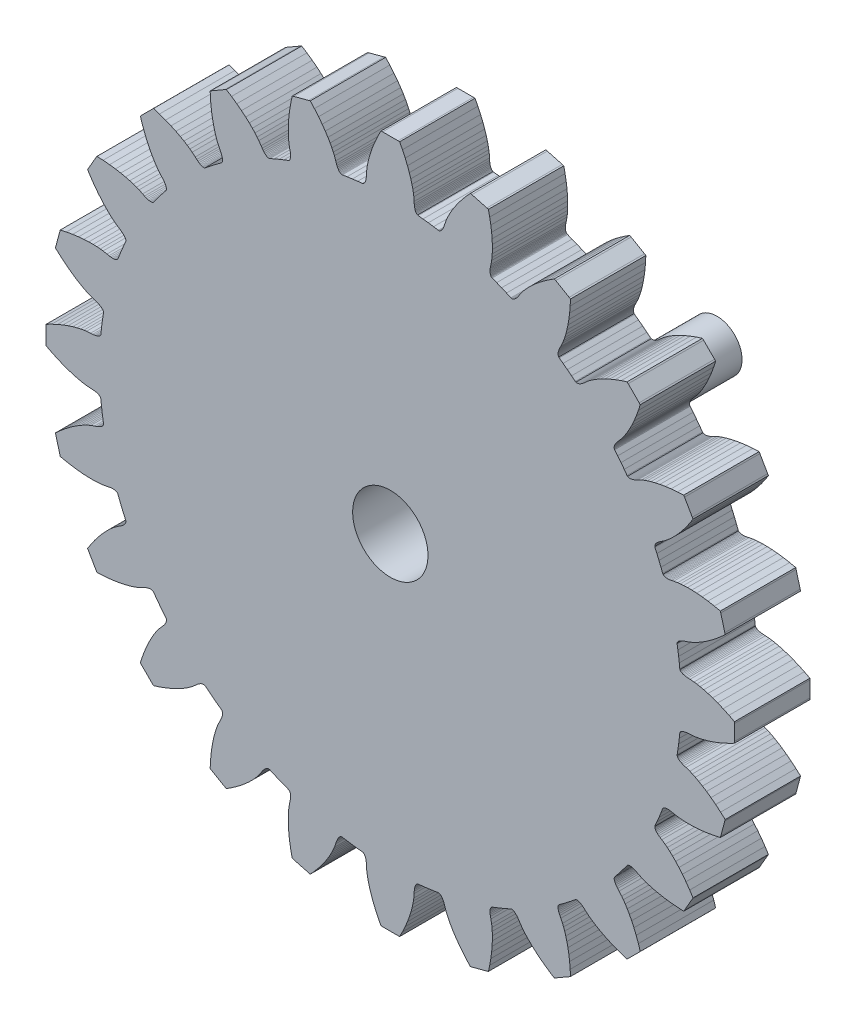
SolidWorks part; units mm, degrees
ref_plane "Front Plane" through (0, 0, 0) normal (0, 0, 1) x (1, 0, 0)
ref_plane "Top Plane" through (0, 0, 0) normal (0, 1, 0) x (1, 0, 0)
ref_plane "Right Plane" through (0, 0, 0) normal (1, 0, 0) x (0, 0, -1)
sketch "Sketch2" plane through (0, 0, 0) normal (0, 0, 1) x (1, 0, 0)
  line L1176 (3.2896, 23.0036) -> (3.0389, 22.7942)
  line L1177 (3.0389, 22.7942) -> (2.8021, 22.6117)
  line L1178 (2.8021, 22.6117) -> (2.5789, 22.4544)
  line L1179 (2.5789, 22.4544) -> (2.3725, 22.3218)
  line L1180 (2.3725, 22.3218) -> (2.182, 22.2103)
  line L1181 (2.182, 22.2103) -> (2.0109, 22.1191)
  line L1182 (2.0109, 22.1191) -> (1.8618, 22.048)
  line L1183 (1.8618, 22.048) -> (1.7314, 21.9922)
  line L1184 (1.7314, 21.9922) -> (1.5416, 21.9241)
  line L1185 (1.5416, 21.9241) -> (1.4393, 21.8922)
  line L1186 (1.4393, 21.8922) -> (1.3698, 21.8662)
  line L1187 (1.3698, 21.8662) -> (1.3083, 21.8387)
  line L1188 (1.3083, 21.8387) -> (1.2546, 21.8097)
  line L1189 (1.2546, 21.8097) -> (1.2083, 21.7799)
  line L1190 (1.2083, 21.7799) -> (1.1698, 21.7495)
  line L1191 (1.1698, 21.7495) -> (1.1387, 21.7184)
  line L1192 (1.1387, 21.7184) -> (1.1155, 21.6879)
  line L1193 (1.1155, 21.6879) -> (1.1004, 21.6575)
  line L1194 (1.1004, 21.6575) -> (1.0924, 21.627)
  line L1195 (1.0924, 21.627) -> (1.093, 21.5916)
  line L1196 (1.093, 21.5916) -> (1.1307, 21.3526)
  line L1197 (1.1307, 21.3526) -> (1.1683, 21.0852)
  line L1198 (1.1683, 21.0852) -> (1.2011, 20.818)
  line L1199 (1.2011, 20.818) -> (1.2264, 20.5774)
  line L1200 (1.2264, 20.5774) -> (1.2351, 20.542)
  line L1201 (1.2351, 20.542) -> (1.2503, 20.5151)
  line L1202 (1.2503, 20.5151) -> (1.2736, 20.4896)
  line L1203 (1.2736, 20.4896) -> (1.304, 20.4665)
  line L1204 (1.304, 20.4665) -> (1.3417, 20.4448)
  line L1205 (1.3417, 20.4448) -> (1.3865, 20.4253)
  line L1206 (1.3865, 20.4253) -> (1.4393, 20.4086)
  line L1207 (1.4393, 20.4086) -> (1.4988, 20.3942)
  line L1208 (1.4988, 20.3942) -> (1.5655, 20.384)
  line L1209 (1.5655, 20.384) -> (1.6388, 20.3767)
  line L1210 (1.6388, 20.3767) -> (1.7459, 20.3724)
  line L1211 (1.7459, 20.3724) -> (1.9474, 20.3558)
  line L1212 (1.9474, 20.3558) -> (2.0872, 20.3354)
  line L1213 (2.0872, 20.3354) -> (2.2499, 20.305)
  line L1214 (2.2499, 20.305) -> (2.4391, 20.2616)
  line L1215 (2.4391, 20.2616) -> (2.6514, 20.203)
  line L1216 (2.6514, 20.203) -> (2.8854, 20.1275)
  line L1217 (2.8854, 20.1275) -> (3.1418, 20.034)
  line L1218 (3.1418, 20.034) -> (3.4178, 19.9188)
  line L1219 (3.4178, 19.9188) -> (3.7134, 19.7813)
  line L1220 (3.7134, 19.7813) -> (3.9915, 19.6379)
  line L1221 (3.9915, 19.6379) -> (3.9938, 19.5596)
  line L1222 (3.9938, 19.5596) -> (3.9938, 18.7742)
  line L1223 (3.9938, 18.7742) -> (3.9915, 18.6954)
  line L1224 (3.9915, 18.6954) -> (3.7134, 18.5525)
  line L1225 (3.7134, 18.5525) -> (3.4178, 18.415)
  line L1226 (3.4178, 18.415) -> (3.1418, 18.2998)
  line L1227 (3.1418, 18.2998) -> (2.8854, 18.2056)
  line L1228 (2.8854, 18.2056) -> (2.6514, 18.131)
  line L1229 (2.6514, 18.131) -> (2.4391, 18.0722)
  line L1230 (2.4391, 18.0722) -> (2.2499, 18.0288)
  line L1231 (2.2499, 18.0288) -> (2.0872, 17.9984)
  line L1232 (2.0872, 17.9984) -> (1.9474, 17.9781)
  line L1233 (1.9474, 17.9781) -> (1.7459, 17.9616)
  line L1234 (1.7459, 17.9616) -> (1.6388, 17.9571)
  line L1235 (1.6388, 17.9571) -> (1.5655, 17.9498)
  line L1236 (1.5655, 17.9498) -> (1.4988, 17.9391)
  line L1237 (1.4988, 17.9391) -> (1.4393, 17.9252)
  line L1238 (1.4393, 17.9252) -> (1.3865, 17.9085)
  line L1239 (1.3865, 17.9085) -> (1.3417, 17.889)
  line L1240 (1.3417, 17.889) -> (1.304, 17.8673)
  line L1241 (1.304, 17.8673) -> (1.2736, 17.8434)
  line L1242 (1.2736, 17.8434) -> (1.2503, 17.818)
  line L1243 (1.2503, 17.818) -> (1.2351, 17.7913)
  line L1244 (1.2351, 17.7913) -> (1.2264, 17.7565)
  line L1245 (1.2264, 17.7565) -> (1.2011, 17.516)
  line L1246 (1.2011, 17.516) -> (1.1683, 17.2478)
  line L1247 (1.1683, 17.2478) -> (1.1307, 16.9813)
  line L1248 (1.1307, 16.9813) -> (1.093, 16.7423)
  line L1249 (1.093, 16.7423) -> (1.0924, 16.706)
  line L1250 (1.0924, 16.706) -> (1.1004, 16.6763)
  line L1251 (1.1004, 16.6763) -> (1.1155, 16.6459)
  line L1252 (1.1155, 16.6459) -> (1.1387, 16.6155)
  line L1253 (1.1387, 16.6155) -> (1.1698, 16.5843)
  line L1254 (1.1698, 16.5843) -> (1.2083, 16.5539)
  line L1255 (1.2083, 16.5539) -> (1.2546, 16.5243)
  line L1256 (1.2546, 16.5243) -> (1.3083, 16.4953)
  line L1257 (1.3083, 16.4953) -> (1.3698, 16.4676)
  line L2458 (1.3698, 16.4676) -> (1.4393, 16.4416)
  line L2459 (1.4393, 16.4416) -> (1.5416, 16.4097)
  line L2460 (1.5416, 16.4097) -> (1.7314, 16.3416)
  line L2461 (1.7314, 16.3416) -> (1.8618, 16.2859)
  line L2462 (1.8618, 16.2859) -> (2.0109, 16.2142)
  line L2463 (2.0109, 16.2142) -> (2.182, 16.1235)
  line L2464 (2.182, 16.1235) -> (2.3725, 16.012)
  line L2465 (2.3725, 16.012) -> (2.5789, 15.8788)
  line L2466 (2.5789, 15.8788) -> (2.8021, 15.7215)
  line L2467 (2.8021, 15.7215) -> (3.0389, 15.5396)
  line L2468 (3.0389, 15.5396) -> (3.2896, 15.3296)
  line L2469 (3.2896, 15.3296) -> (3.5207, 15.1195)
  line L2470 (3.5207, 15.1195) -> (3.5018, 15.0434)
  line L2471 (3.5018, 15.0434) -> (3.2991, 14.2842)
  line L2472 (3.2991, 14.2842) -> (3.2766, 14.2089)
  line L2473 (3.2766, 14.2089) -> (2.9715, 14.1429)
  line L2474 (2.9715, 14.1429) -> (2.65, 14.0864)
  line L2475 (2.65, 14.0864) -> (2.3537, 14.0466)
  line L2476 (2.3537, 14.0466) -> (2.0811, 14.0219)
  line L2477 (2.0811, 14.0219) -> (1.8364, 14.0105)
  line L2478 (1.8364, 14.0105) -> (1.6155, 14.009)
  line L2479 (1.6155, 14.009) -> (1.4221, 14.0155)
  line L2480 (1.4221, 14.0155) -> (1.2569, 14.0285)
  line L2481 (1.2569, 14.0285) -> (1.1163, 14.0452)
  line L2482 (1.1163, 14.0452) -> (0.9179, 14.0814)
  line L2483 (0.9179, 14.0814) -> (0.8126, 14.1046)
  line L2484 (0.8126, 14.1046) -> (0.7404, 14.1169)
  line L2485 (0.7404, 14.1169) -> (0.6731, 14.1234)
  line L2486 (0.6731, 14.1234) -> (0.6121, 14.1256)
  line L2487 (0.6121, 14.1256) -> (0.5572, 14.1226)
  line L2488 (0.5572, 14.1226) -> (0.5086, 14.1162)
  line L2489 (0.5086, 14.1162) -> (0.4664, 14.1046)
  line L2490 (0.4664, 14.1046) -> (0.431, 14.0894)
  line L2491 (0.431, 14.0894) -> (0.402, 14.0712)
  line L2492 (0.402, 14.0712) -> (0.3801, 14.0488)
  line L2493 (0.3801, 14.0488) -> (0.3629, 14.0177)
  line L2494 (0.3629, 14.0177) -> (0.276, 13.7916)
  line L2495 (0.276, 13.7916) -> (0.1753, 13.5416)
  line L2496 (0.1753, 13.5416) -> (0.0703, 13.2939)
  line L2497 (0.0703, 13.2939) -> (-0.0283, 13.0723)
  line L2498 (-0.0283, 13.0723) -> (-0.0383, 13.0382)
  line L2499 (-0.0383, 13.0382) -> (-0.0383, 13.007)
  line L2500 (-0.0383, 13.007) -> (-0.0311, 12.9737)
  line L2501 (-0.0311, 12.9737) -> (-0.0167, 12.9376)
  line L2502 (-0.0167, 12.9376) -> (0.0051, 12.8999)
  line L2503 (0.0051, 12.8999) -> (0.0339, 12.8608)
  line L2504 (0.0339, 12.8608) -> (0.0709, 12.8202)
  line L2505 (0.0709, 12.8202) -> (0.1159, 12.7781)
  line L2506 (0.1159, 12.7781) -> (0.1681, 12.7354)
  line L2507 (0.1681, 12.7354) -> (0.2282, 12.6927)
  line L2508 (0.2282, 12.6927) -> (0.3186, 12.6354)
  line L2509 (0.3186, 12.6354) -> (0.4846, 12.5202)
  line L2510 (0.4846, 12.5202) -> (0.5955, 12.4326)
  line L2511 (0.5955, 12.4326) -> (0.7214, 12.3254)
  line L2512 (0.7214, 12.3254) -> (0.8635, 12.1928)
  line L2513 (0.8635, 12.1928) -> (1.0185, 12.0356)
  line L2514 (1.0185, 12.0356) -> (1.1836, 11.8538)
  line L2515 (1.1836, 11.8538) -> (1.3582, 11.6444)
  line L2516 (1.3582, 11.6444) -> (1.5401, 11.4068)
  line L2517 (1.5401, 11.4068) -> (1.727, 11.1395)
  line L2518 (1.727, 11.1395) -> (1.8965, 10.8765)
  line L2519 (1.8965, 10.8765) -> (1.8588, 10.8077)
  line L2520 (1.8588, 10.8077) -> (1.4663, 10.1281)
  line L2521 (1.4663, 10.1281) -> (1.4257, 10.0608)
  line L2522 (1.4257, 10.0608) -> (1.1128, 10.0753)
  line L2523 (1.1128, 10.0753) -> (0.7882, 10.1042)
  line L2524 (0.7882, 10.1042) -> (0.4911, 10.1426)
  line L2525 (0.4911, 10.1426) -> (0.2224, 10.1897)
  line L2526 (0.2224, 10.1897) -> (-0.0174, 10.2412)
  line L2527 (-0.0174, 10.2412) -> (-0.231, 10.2969)
  line L2528 (-0.231, 10.2969) -> (-0.4165, 10.3542)
  line L2529 (-0.4165, 10.3542) -> (-0.573, 10.4092)
  line L2530 (-0.573, 10.4092) -> (-0.7041, 10.4614)
  line L2531 (-0.7041, 10.4614) -> (-0.8868, 10.5476)
  line L2532 (-0.8868, 10.5476) -> (-0.9816, 10.5976)
  line L2533 (-0.9816, 10.5976) -> (-1.0492, 10.628)
  line L2534 (-1.0492, 10.628) -> (-1.1119, 10.6519)
  line L2535 (-1.1119, 10.6519) -> (-1.1708, 10.6693)
  line L2536 (-1.1708, 10.6693) -> (-1.2243, 10.6809)
  line L2537 (-1.2243, 10.6809) -> (-1.2729, 10.6867)
  line L2538 (-1.2729, 10.6867) -> (-1.3163, 10.6867)
  line L2539 (-1.3163, 10.6867) -> (-1.3548, 10.6816)
  line L2540 (-1.3548, 10.6816) -> (-1.3874, 10.6715)
  line L2541 (-1.3874, 10.6715) -> (-1.4141, 10.6555)
  line L2542 (-1.4141, 10.6555) -> (-1.4388, 10.6295)
  line L2543 (-1.4388, 10.6295) -> (-1.5809, 10.4339)
  line L2544 (-1.5809, 10.4339) -> (-1.7431, 10.2187)
  line L2545 (-1.7431, 10.2187) -> (-1.9089, 10.0064)
  line L2546 (-1.9089, 10.0064) -> (-2.0618, 9.8181)
  line L2547 (-2.0618, 9.8181) -> (-2.0799, 9.7877)
  line L2548 (-2.0799, 9.7877) -> (-2.0885, 9.7572)
  line L2549 (-2.0885, 9.7572) -> (-2.09, 9.7232)
  line L2550 (-2.09, 9.7232) -> (-2.0856, 9.6848)
  line L2551 (-2.0856, 9.6848) -> (-2.0741, 9.6428)
  line L2552 (-2.0741, 9.6428) -> (-2.056, 9.5971)
  line L2553 (-2.056, 9.5971) -> (-2.0307, 9.5486)
  line L2554 (-2.0307, 9.5486) -> (-1.9988, 9.4964)
  line L2555 (-1.9988, 9.4964) -> (-1.959, 9.4421)
  line L2556 (-1.959, 9.4421) -> (-1.9119, 9.3849)
  line L2557 (-1.9119, 9.3849) -> (-1.8394, 9.3059)
  line L2558 (-1.8394, 9.3059) -> (-1.7089, 9.1516)
  line L2559 (-1.7089, 9.1516) -> (-1.6243, 9.0386)
  line L2560 (-1.6243, 9.0386) -> (-1.5308, 8.9017)
  line L2561 (-1.5308, 8.9017) -> (-1.428, 8.7372)
  line L2562 (-1.428, 8.7372) -> (-1.3186, 8.546)
  line L2563 (-1.3186, 8.546) -> (-1.2062, 8.3272)
  line L2564 (-1.2062, 8.3272) -> (-1.0917, 8.0794)
  line L2565 (-1.0917, 8.0794) -> (-0.9773, 7.8034)
  line L2566 (-0.9773, 7.8034) -> (-0.8657, 7.497)
  line L2567 (-0.8657, 7.497) -> (-0.7709, 7.1985)
  line L2568 (-0.7709, 7.1985) -> (-0.8252, 7.142)
  line L2569 (-0.8252, 7.142) -> (-1.3802, 6.5871)
  line L2570 (-1.3802, 6.5871) -> (-1.4365, 6.5328)
  line L2571 (-1.4365, 6.5328) -> (-1.7351, 6.6277)
  line L2572 (-1.7351, 6.6277) -> (-2.0415, 6.7392)
  line L2573 (-2.0415, 6.7392) -> (-2.3174, 6.8537)
  line L2574 (-2.3174, 6.8537) -> (-2.5652, 6.9682)
  line L2575 (-2.5652, 6.9682) -> (-2.7841, 7.0805)
  line L2576 (-2.7841, 7.0805) -> (-2.9753, 7.1898)
  line L2577 (-2.9753, 7.1898) -> (-3.1398, 7.2927)
  line L2578 (-3.1398, 7.2927) -> (-3.2767, 7.3862)
  line L2579 (-3.2767, 7.3862) -> (-3.3898, 7.4709)
  line L2580 (-3.3898, 7.4709) -> (-3.544, 7.6013)
  line L2581 (-3.544, 7.6013) -> (-3.623, 7.6738)
  line L2582 (-3.623, 7.6738) -> (-3.6802, 7.7209)
  line L2583 (-3.6802, 7.7209) -> (-3.7345, 7.7607)
  line L2584 (-3.7345, 7.7607) -> (-3.7866, 7.7926)
  line L2585 (-3.7866, 7.7926) -> (-3.8352, 7.8179)
  line L2586 (-3.8352, 7.8179) -> (-3.8809, 7.836)
  line L2587 (-3.8809, 7.836) -> (-3.9229, 7.8476)
  line L2588 (-3.9229, 7.8476) -> (-3.9613, 7.852)
  line L2589 (-3.9613, 7.852) -> (-3.9953, 7.8505)
  line L2590 (-3.9953, 7.8505) -> (-4.0256, 7.8418)
  line L2591 (-4.0256, 7.8418) -> (-4.0561, 7.8237)
  line L2592 (-4.0561, 7.8237) -> (-4.2445, 7.6709)
  line L2593 (-4.2445, 7.6709) -> (-4.4569, 7.505)
  line L2594 (-4.4569, 7.505) -> (-4.672, 7.3427)
  line L2595 (-4.672, 7.3427) -> (-4.8674, 7.2007)
  line L2596 (-4.8674, 7.2007) -> (-4.8936, 7.1761)
  line L2597 (-4.8936, 7.1761) -> (-4.9096, 7.1493)
  line L2598 (-4.9096, 7.1493) -> (-4.9197, 7.1167)
  line L2599 (-4.9197, 7.1167) -> (-4.9248, 7.0783)
  line L2600 (-4.9248, 7.0783) -> (-4.9248, 7.0348)
  line L2601 (-4.9248, 7.0348) -> (-4.9191, 6.9863)
  line L2602 (-4.9191, 6.9863) -> (-4.9073, 6.9327)
  line L2603 (-4.9073, 6.9327) -> (-4.8901, 6.874)
  line L2604 (-4.8901, 6.874) -> (-4.8662, 6.8109)
  line L2605 (-4.8662, 6.8109) -> (-4.8357, 6.7436)
  line L2606 (-4.8357, 6.7436) -> (-4.7857, 6.6487)
  line L2607 (-4.7857, 6.6487) -> (-4.6994, 6.4661)
  line L2608 (-4.6994, 6.4661) -> (-4.6473, 6.335)
  line L2609 (-4.6473, 6.335) -> (-4.5922, 6.1785)
  line L2610 (-4.5922, 6.1785) -> (-4.5349, 5.9931)
  line L2611 (-4.5349, 5.9931) -> (-4.4794, 5.7793)
  line L2612 (-4.4794, 5.7793) -> (-4.4277, 5.5396)
  line L2613 (-4.4277, 5.5396) -> (-4.3807, 5.2708)
  line L2614 (-4.3807, 5.2708) -> (-4.3422, 4.9738)
  line L2615 (-4.3422, 4.9738) -> (-4.3134, 4.6492)
  line L2616 (-4.3134, 4.6492) -> (-4.2988, 4.3363)
  line L2617 (-4.2988, 4.3363) -> (-4.3661, 4.2957)
  line L2618 (-4.3661, 4.2957) -> (-5.0456, 3.9031)
  line L2619 (-5.0456, 3.9031) -> (-5.1144, 3.8654)
  line L2620 (-5.1144, 3.8654) -> (-5.3775, 4.0349)
  line L2621 (-5.3775, 4.0349) -> (-5.6449, 4.2218)
  line L2622 (-5.6449, 4.2218) -> (-5.8825, 4.4037)
  line L2623 (-5.8825, 4.4037) -> (-6.0918, 4.5782)
  line L2624 (-6.0918, 4.5782) -> (-6.2736, 4.7434)
  line L2625 (-6.2736, 4.7434) -> (-6.4309, 4.8984)
  line L2626 (-6.4309, 4.8984) -> (-6.5635, 5.0404)
  line L2627 (-6.5635, 5.0404) -> (-6.6707, 5.1665)
  line L2628 (-6.6707, 5.1665) -> (-6.7584, 5.2773)
  line L2629 (-6.7584, 5.2773) -> (-6.8735, 5.4432)
  line L2630 (-6.8735, 5.4432) -> (-6.9307, 5.5338)
  line L2631 (-6.9307, 5.5338) -> (-6.9735, 5.5939)
  line L2632 (-6.9735, 5.5939) -> (-7.0161, 5.6461)
  line L2633 (-7.0161, 5.6461) -> (-7.0582, 5.691)
  line L2634 (-7.0582, 5.691) -> (-7.0989, 5.7279)
  line L2635 (-7.0989, 5.7279) -> (-7.138, 5.7569)
  line L2636 (-7.138, 5.7569) -> (-7.1757, 5.7786)
  line L2637 (-7.1757, 5.7786) -> (-7.2117, 5.7931)
  line L2638 (-7.2117, 5.7931) -> (-7.2451, 5.8004)
  line L2639 (-7.2451, 5.8004) -> (-7.2764, 5.8004)
  line L2640 (-7.2764, 5.8004) -> (-7.3103, 5.7902)
  line L2641 (-7.3103, 5.7902) -> (-7.5321, 5.6917)
  line L2642 (-7.5321, 5.6917) -> (-7.7799, 5.5867)
  line L2643 (-7.7799, 5.5867) -> (-8.0296, 5.486)
  line L2644 (-8.0296, 5.486) -> (-8.2557, 5.399)
  line L2645 (-8.2557, 5.399) -> (-8.2869, 5.3816)
  line L2646 (-8.2869, 5.3816) -> (-8.3093, 5.3599)
  line L2647 (-8.3093, 5.3599) -> (-8.3275, 5.3309)
  line L2648 (-8.3275, 5.3309) -> (-8.3427, 5.2954)
  line L2649 (-8.3427, 5.2954) -> (-8.3542, 5.2534)
  line L2650 (-8.3542, 5.2534) -> (-8.3607, 5.2049)
  line L2651 (-8.3607, 5.2049) -> (-8.3637, 5.1498)
  line L2652 (-8.3637, 5.1498) -> (-8.3614, 5.089)
  line L2653 (-8.3614, 5.089) -> (-8.355, 5.0216)
  line L2654 (-8.355, 5.0216) -> (-8.3427, 4.9492)
  line L2655 (-8.3427, 4.9492) -> (-8.3195, 4.8441)
  line L2656 (-8.3195, 4.8441) -> (-8.2832, 4.6456)
  line L2657 (-8.2832, 4.6456) -> (-8.2666, 4.5051)
  line L2658 (-8.2666, 4.5051) -> (-8.2535, 4.3399)
  line L2659 (-8.2535, 4.3399) -> (-8.247, 4.1465)
  line L2660 (-8.247, 4.1465) -> (-8.2485, 3.9255)
  line L2661 (-8.2485, 3.9255) -> (-8.2599, 3.6807)
  line L2662 (-8.2599, 3.6807) -> (-8.2846, 3.4083)
  line L2663 (-8.2846, 3.4083) -> (-8.3246, 3.112)
  line L2664 (-8.3246, 3.112) -> (-8.381, 2.7903)
  line L2665 (-8.381, 2.7903) -> (-8.4469, 2.4853)
  line L2666 (-8.4469, 2.4853) -> (-8.5222, 2.4629)
  line L2667 (-8.5222, 2.4629) -> (-9.2814, 2.2601)
  line L2668 (-9.2814, 2.2601) -> (-9.3575, 2.2412)
  line L2669 (-9.3575, 2.2412) -> (-9.5676, 2.4723)
  line L2670 (-9.5676, 2.4723) -> (-9.7777, 2.723)
  line L2671 (-9.7777, 2.723) -> (-9.9595, 2.9598)
  line L2672 (-9.9595, 2.9598) -> (-10.1168, 3.183)
  line L2673 (-10.1168, 3.183) -> (-10.2502, 3.3894)
  line L2674 (-10.2502, 3.3894) -> (-10.3615, 3.58)
  line L2675 (-10.3615, 3.58) -> (-10.4523, 3.7509)
  line L2676 (-10.4523, 3.7509) -> (-10.5239, 3.9002)
  line L2677 (-10.5239, 3.9002) -> (-10.5797, 4.0306)
  line L2678 (-10.5797, 4.0306) -> (-10.6477, 4.2204)
  line L2679 (-10.6477, 4.2204) -> (-10.6796, 4.3225)
  line L2680 (-10.6796, 4.3225) -> (-10.7058, 4.3921)
  line L2681 (-10.7058, 4.3921) -> (-10.7333, 4.4536)
  line L2682 (-10.7333, 4.4536) -> (-10.7624, 4.5072)
  line L2683 (-10.7624, 4.5072) -> (-10.792, 4.5536)
  line L2684 (-10.792, 4.5536) -> (-10.8225, 4.592)
  line L2685 (-10.8225, 4.592) -> (-10.8536, 4.6232)
  line L2686 (-10.8536, 4.6232) -> (-10.884, 4.6463)
  line L2687 (-10.884, 4.6463) -> (-10.9145, 4.6616)
  line L2688 (-10.9145, 4.6616) -> (-10.9441, 4.6695)
  line L2689 (-10.9441, 4.6695) -> (-10.9803, 4.6688)
  line L2690 (-10.9803, 4.6688) -> (-11.2193, 4.6311)
  line L2691 (-11.2193, 4.6311) -> (-11.486, 4.5935)
  line L2692 (-11.486, 4.5935) -> (-11.754, 4.5608)
  line L2693 (-11.754, 4.5608) -> (-11.9946, 4.5355)
  line L2694 (-11.9946, 4.5355) -> (-12.0294, 4.5268)
  line L2695 (-12.0294, 4.5268) -> (-12.0561, 4.5116)
  line L2696 (-12.0561, 4.5116) -> (-12.0815, 4.4884)
  line L2697 (-12.0815, 4.4884) -> (-12.1054, 4.458)
  line L2698 (-12.1054, 4.458) -> (-12.1272, 4.4203)
  line L2699 (-12.1272, 4.4203) -> (-12.1465, 4.3754)
  line L2700 (-12.1465, 4.3754) -> (-12.1632, 4.3225)
  line L2701 (-12.1632, 4.3225) -> (-12.1772, 4.2631)
  line L2702 (-12.1772, 4.2631) -> (-12.1879, 4.1965)
  line L2703 (-12.1879, 4.1965) -> (-12.1951, 4.1233)
  line L2704 (-12.1951, 4.1233) -> (-12.1997, 4.0161)
  line L2705 (-12.1997, 4.0161) -> (-12.2161, 3.8147)
  line L2706 (-12.2161, 3.8147) -> (-12.2365, 3.6749)
  line L2707 (-12.2365, 3.6749) -> (-12.267, 3.5119)
  line L2708 (-12.267, 3.5119) -> (-12.3104, 3.3228)
  line L2709 (-12.3104, 3.3228) -> (-12.3691, 3.1105)
  line L2710 (-12.3691, 3.1105) -> (-12.4436, 2.8765)
  line L2711 (-12.4436, 2.8765) -> (-12.5379, 2.6201)
  line L2712 (-12.5379, 2.6201) -> (-12.653, 2.3441)
  line L2713 (-12.653, 2.3441) -> (-12.7907, 2.0485)
  line L2714 (-12.7907, 2.0485) -> (-12.9334, 1.7703)
  line L2715 (-12.9334, 1.7703) -> (-13.0123, 1.7681)
  line L2716 (-13.0123, 1.7681) -> (-13.7977, 1.7681)
  line L2717 (-13.7977, 1.7681) -> (-13.876, 1.7703)
  line L2718 (-13.876, 1.7703) -> (-14.0193, 2.0485)
  line L2719 (-14.0193, 2.0485) -> (-14.1569, 2.3441)
  line L2720 (-14.1569, 2.3441) -> (-14.272, 2.6201)
  line L2721 (-14.272, 2.6201) -> (-14.3655, 2.8765)
  line L2722 (-14.3655, 2.8765) -> (-14.4411, 3.1105)
  line L2723 (-14.4411, 3.1105) -> (-14.4997, 3.3228)
  line L2724 (-14.4997, 3.3228) -> (-14.5431, 3.5119)
  line L2725 (-14.5431, 3.5119) -> (-14.5735, 3.6749)
  line L2726 (-14.5735, 3.6749) -> (-14.5938, 3.8147)
  line L2727 (-14.5938, 3.8147) -> (-14.6105, 4.0161)
  line L2728 (-14.6105, 4.0161) -> (-14.6148, 4.1233)
  line L2729 (-14.6148, 4.1233) -> (-14.622, 4.1965)
  line L2730 (-14.622, 4.1965) -> (-14.6322, 4.2631)
  line L2731 (-14.6322, 4.2631) -> (-14.6467, 4.3225)
  line L2732 (-14.6467, 4.3225) -> (-14.6634, 4.3754)
  line L2733 (-14.6634, 4.3754) -> (-14.6829, 4.4203)
  line L2734 (-14.6829, 4.4203) -> (-14.7047, 4.458)
  line L2735 (-14.7047, 4.458) -> (-14.7278, 4.4884)
  line L2736 (-14.7278, 4.4884) -> (-14.7533, 4.5116)
  line L2737 (-14.7533, 4.5116) -> (-14.78, 4.5268)
  line L2738 (-14.78, 4.5268) -> (-14.8155, 4.5355)
  line L2739 (-14.8155, 4.5355) -> (-15.056, 4.5608)
  line L2740 (-15.056, 4.5608) -> (-15.3233, 4.5935)
  line L2741 (-15.3233, 4.5935) -> (-15.5906, 4.6311)
  line L2742 (-15.5906, 4.6311) -> (-15.8296, 4.6688)
  line L2743 (-15.8296, 4.6688) -> (-15.8652, 4.6695)
  line L2744 (-15.8652, 4.6695) -> (-15.8956, 4.6616)
  line L2745 (-15.8956, 4.6616) -> (-15.926, 4.6463)
  line L2746 (-15.926, 4.6463) -> (-15.9565, 4.6232)
  line L2747 (-15.9565, 4.6232) -> (-15.9876, 4.592)
  line L2748 (-15.9876, 4.592) -> (-16.018, 4.5536)
  line L2749 (-16.018, 4.5536) -> (-16.0478, 4.5072)
  line L2750 (-16.0478, 4.5072) -> (-16.0768, 4.4536)
  line L2751 (-16.0768, 4.4536) -> (-16.1043, 4.3921)
  line L2752 (-16.1043, 4.3921) -> (-16.1303, 4.3225)
  line L2753 (-16.1303, 4.3225) -> (-16.1623, 4.2204)
  line L2754 (-16.1623, 4.2204) -> (-16.2304, 4.0306)
  line L2755 (-16.2304, 4.0306) -> (-16.286, 3.9002)
  line L2756 (-16.286, 3.9002) -> (-16.3571, 3.7509)
  line L2757 (-16.3571, 3.7509) -> (-16.4484, 3.58)
  line L2758 (-16.4484, 3.58) -> (-16.5599, 3.3894)
  line L2759 (-16.5599, 3.3894) -> (-16.6925, 3.183)
  line L2760 (-16.6925, 3.183) -> (-16.8497, 2.9598)
  line L2761 (-16.8497, 2.9598) -> (-17.0323, 2.723)
  line L2762 (-17.0323, 2.723) -> (-17.2416, 2.4723)
  line L2763 (-17.2416, 2.4723) -> (-17.4524, 2.2412)
  line L2764 (-17.4524, 2.2412) -> (-17.5292, 2.2601)
  line L2765 (-17.5292, 2.2601) -> (-18.2878, 2.4629)
  line L2766 (-18.2878, 2.4629) -> (-18.3624, 2.4853)
  line L2767 (-18.3624, 2.4853) -> (-18.429, 2.7903)
  line L2768 (-18.429, 2.7903) -> (-18.4855, 3.112)
  line L2769 (-18.4855, 3.112) -> (-18.5246, 3.4083)
  line L2770 (-18.5246, 3.4083) -> (-18.5492, 3.6807)
  line L2771 (-18.5492, 3.6807) -> (-18.5615, 3.9255)
  line L2772 (-18.5615, 3.9255) -> (-18.563, 4.1465)
  line L2773 (-18.563, 4.1465) -> (-18.5557, 4.3399)
  line L2774 (-18.5557, 4.3399) -> (-18.5435, 4.5051)
  line L2775 (-18.5435, 4.5051) -> (-18.5261, 4.6456)
  line L2776 (-18.5261, 4.6456) -> (-18.4906, 4.8441)
  line L2777 (-18.4906, 4.8441) -> (-18.4667, 4.9492)
  line L2778 (-18.4667, 4.9492) -> (-18.4551, 5.0216)
  line L2779 (-18.4551, 5.0216) -> (-18.4479, 5.089)
  line L2780 (-18.4479, 5.089) -> (-18.4464, 5.1498)
  line L2781 (-18.4464, 5.1498) -> (-18.4485, 5.2049)
  line L2782 (-18.4485, 5.2049) -> (-18.4557, 5.2534)
  line L2783 (-18.4557, 5.2534) -> (-18.4674, 5.2954)
  line L2784 (-18.4674, 5.2954) -> (-18.4819, 5.3309)
  line L2785 (-18.4819, 5.3309) -> (-18.5007, 5.3599)
  line L2786 (-18.5007, 5.3599) -> (-18.5225, 5.3816)
  line L2787 (-18.5225, 5.3816) -> (-18.5543, 5.399)
  line L2788 (-18.5543, 5.399) -> (-18.7803, 5.486)
  line L2789 (-18.7803, 5.486) -> (-19.0303, 5.5867)
  line L2790 (-19.0303, 5.5867) -> (-19.278, 5.6917)
  line L2791 (-19.278, 5.6917) -> (-19.499, 5.7902)
  line L2792 (-19.499, 5.7902) -> (-19.5337, 5.8004)
  line L2793 (-19.5337, 5.8004) -> (-19.565, 5.8004)
  line L2794 (-19.565, 5.8004) -> (-19.5982, 5.7931)
  line L2795 (-19.5982, 5.7931) -> (-19.6337, 5.7786)
  line L2796 (-19.6337, 5.7786) -> (-19.6714, 5.7569)
  line L2797 (-19.6714, 5.7569) -> (-19.7112, 5.7279)
  line L2798 (-19.7112, 5.7279) -> (-19.7518, 5.691)
  line L2799 (-19.7518, 5.691) -> (-19.7938, 5.6461)
  line L2800 (-19.7938, 5.6461) -> (-19.8358, 5.5939)
  line L2801 (-19.8358, 5.5939) -> (-19.8793, 5.5338)
  line L2802 (-19.8793, 5.5338) -> (-19.9365, 5.4432)
  line L2803 (-19.9365, 5.4432) -> (-20.0517, 5.2773)
  line L2804 (-20.0517, 5.2773) -> (-20.1386, 5.1665)
  line L2805 (-20.1386, 5.1665) -> (-20.2466, 5.0404)
  line L2806 (-20.2466, 5.0404) -> (-20.3792, 4.8984)
  line L2807 (-20.3792, 4.8984) -> (-20.5356, 4.7434)
  line L2808 (-20.5356, 4.7434) -> (-20.7175, 4.5782)
  line L2809 (-20.7175, 4.5782) -> (-20.9276, 4.4037)
  line L2810 (-20.9276, 4.4037) -> (-21.1645, 4.2218)
  line L2811 (-21.1645, 4.2218) -> (-21.4318, 4.0349)
  line L2812 (-21.4318, 4.0349) -> (-21.6955, 3.8654)
  line L2813 (-21.6955, 3.8654) -> (-21.765, 3.9031)
  line L2814 (-21.765, 3.9031) -> (-22.4445, 4.2957)
  line L2815 (-22.4445, 4.2957) -> (-22.5112, 4.3363)
  line L2816 (-22.5112, 4.3363) -> (-22.496, 4.6492)
  line L2817 (-22.496, 4.6492) -> (-22.4677, 4.9738)
  line L2818 (-22.4677, 4.9738) -> (-22.4286, 5.2708)
  line L2819 (-22.4286, 5.2708) -> (-22.3822, 5.5396)
  line L2820 (-22.3822, 5.5396) -> (-22.3301, 5.7793)
  line L2821 (-22.3301, 5.7793) -> (-22.2743, 5.9931)
  line L2822 (-22.2743, 5.9931) -> (-22.2178, 6.1785)
  line L2823 (-22.2178, 6.1785) -> (-22.1627, 6.335)
  line L2824 (-22.1627, 6.335) -> (-22.1106, 6.4661)
  line L2825 (-22.1106, 6.4661) -> (-22.0244, 6.6487)
  line L2826 (-22.0244, 6.6487) -> (-21.9744, 6.7436)
  line L2827 (-21.9744, 6.7436) -> (-21.9439, 6.8109)
  line L2828 (-21.9439, 6.8109) -> (-21.92, 6.874)
  line L2829 (-21.92, 6.874) -> (-21.9019, 6.9327)
  line L2830 (-21.9019, 6.9327) -> (-21.8903, 6.9863)
  line L2831 (-21.8903, 6.9863) -> (-21.8846, 7.0348)
  line L2832 (-21.8846, 7.0348) -> (-21.8846, 7.0783)
  line L2833 (-21.8846, 7.0783) -> (-21.8903, 7.1167)
  line L2834 (-21.8903, 7.1167) -> (-21.9005, 7.1493)
  line L2835 (-21.9005, 7.1493) -> (-21.9164, 7.1761)
  line L2836 (-21.9164, 7.1761) -> (-21.9418, 7.2007)
  line L2837 (-21.9418, 7.2007) -> (-22.1381, 7.3427)
  line L2838 (-22.1381, 7.3427) -> (-22.3532, 7.505)
  line L2839 (-22.3532, 7.505) -> (-22.5655, 7.6709)
  line L2840 (-22.5655, 7.6709) -> (-22.7539, 7.8237)
  line L2841 (-22.7539, 7.8237) -> (-22.7843, 7.8418)
  line L2842 (-22.7843, 7.8418) -> (-22.814, 7.8505)
  line L2843 (-22.814, 7.8505) -> (-22.8488, 7.852)
  line L2844 (-22.8488, 7.852) -> (-22.8864, 7.8476)
  line L2845 (-22.8864, 7.8476) -> (-22.9285, 7.836)
  line L2846 (-22.9285, 7.836) -> (-22.9741, 7.8179)
  line L2847 (-22.9741, 7.8179) -> (-23.0234, 7.7926)
  line L2848 (-23.0234, 7.7926) -> (-23.0755, 7.7607)
  line L2849 (-23.0755, 7.7607) -> (-23.1298, 7.7209)
  line L2850 (-23.1298, 7.7209) -> (-23.1871, 7.6738)
  line L2851 (-23.1871, 7.6738) -> (-23.266, 7.6013)
  line L2852 (-23.266, 7.6013) -> (-23.4196, 7.4709)
  line L2853 (-23.4196, 7.4709) -> (-23.5334, 7.3862)
  line L2854 (-23.5334, 7.3862) -> (-23.6696, 7.2927)
  line L2855 (-23.6696, 7.2927) -> (-23.834, 7.1898)
  line L2856 (-23.834, 7.1898) -> (-24.026, 7.0805)
  line L2857 (-24.026, 7.0805) -> (-24.244, 6.9682)
  line L2858 (-24.244, 6.9682) -> (-24.4918, 6.8537)
  line L2859 (-24.4918, 6.8537) -> (-24.7685, 6.7392)
  line L2860 (-24.7685, 6.7392) -> (-25.075, 6.6277)
  line L2861 (-25.075, 6.6277) -> (-25.3727, 6.5328)
  line L2862 (-25.3727, 6.5328) -> (-25.4299, 6.5871)
  line L2863 (-25.4299, 6.5871) -> (-25.9856, 7.142)
  line L2864 (-25.9856, 7.142) -> (-26.0392, 7.1985)
  line L2865 (-26.0392, 7.1985) -> (-25.9443, 7.497)
  line L2866 (-25.9443, 7.497) -> (-25.832, 7.8034)
  line L2867 (-25.832, 7.8034) -> (-25.7183, 8.0794)
  line L2868 (-25.7183, 8.0794) -> (-25.6031, 8.3272)
  line L2869 (-25.6031, 8.3272) -> (-25.4908, 8.546)
  line L2870 (-25.4908, 8.546) -> (-25.3821, 8.7372)
  line L2871 (-25.3821, 8.7372) -> (-25.2793, 8.9017)
  line L2872 (-25.2793, 8.9017) -> (-25.1858, 9.0386)
  line L2873 (-25.1858, 9.0386) -> (-25.101, 9.1516)
  line L2874 (-25.101, 9.1516) -> (-24.9706, 9.3059)
  line L2875 (-24.9706, 9.3059) -> (-24.8975, 9.3849)
  line L2876 (-24.8975, 9.3849) -> (-24.8511, 9.4421)
  line L2877 (-24.8511, 9.4421) -> (-24.8113, 9.4964)
  line L2878 (-24.8113, 9.4964) -> (-24.7794, 9.5486)
  line L2879 (-24.7794, 9.5486) -> (-24.754, 9.5971)
  line L2880 (-24.754, 9.5971) -> (-24.7359, 9.6428)
  line L2881 (-24.7359, 9.6428) -> (-24.7243, 9.6848)
  line L2882 (-24.7243, 9.6848) -> (-24.72, 9.7232)
  line L2883 (-24.72, 9.7232) -> (-24.7214, 9.7572)
  line L2884 (-24.7214, 9.7572) -> (-24.7294, 9.7877)
  line L2885 (-24.7294, 9.7877) -> (-24.7482, 9.8181)
  line L2886 (-24.7482, 9.8181) -> (-24.9004, 10.0064)
  line L2887 (-24.9004, 10.0064) -> (-25.0663, 10.2187)
  line L2888 (-25.0663, 10.2187) -> (-25.2285, 10.4339)
  line L2889 (-25.2285, 10.4339) -> (-25.3713, 10.6295)
  line L2890 (-25.3713, 10.6295) -> (-25.3959, 10.6555)
  line L2891 (-25.3959, 10.6555) -> (-25.4227, 10.6715)
  line L2892 (-25.4227, 10.6715) -> (-25.4553, 10.6816)
  line L2893 (-25.4553, 10.6816) -> (-25.493, 10.6867)
  line L2894 (-25.493, 10.6867) -> (-25.5372, 10.6867)
  line L2895 (-25.5372, 10.6867) -> (-25.5857, 10.6809)
  line L2896 (-25.5857, 10.6809) -> (-25.6393, 10.6693)
  line L2897 (-25.6393, 10.6693) -> (-25.698, 10.6519)
  line L2898 (-25.698, 10.6519) -> (-25.761, 10.628)
  line L2899 (-25.761, 10.628) -> (-25.8284, 10.5976)
  line L2900 (-25.8284, 10.5976) -> (-25.9233, 10.5476)
  line L2901 (-25.9233, 10.5476) -> (-26.1058, 10.4614)
  line L2902 (-26.1058, 10.4614) -> (-26.237, 10.4092)
  line L2903 (-26.237, 10.4092) -> (-26.3934, 10.3542)
  line L2904 (-26.3934, 10.3542) -> (-26.5789, 10.2969)
  line L2905 (-26.5789, 10.2969) -> (-26.7919, 10.2412)
  line L2906 (-26.7919, 10.2412) -> (-27.0324, 10.1897)
  line L2907 (-27.0324, 10.1897) -> (-27.3012, 10.1426)
  line L2908 (-27.3012, 10.1426) -> (-27.5975, 10.1042)
  line L2909 (-27.5975, 10.1042) -> (-27.9227, 10.0753)
  line L2910 (-27.9227, 10.0753) -> (-28.235, 10.0608)
  line L2911 (-28.235, 10.0608) -> (-28.2762, 10.1281)
  line L2912 (-28.2762, 10.1281) -> (-28.6696, 10.8077)
  line L2913 (-28.6696, 10.8077) -> (-28.7066, 10.8765)
  line L2914 (-28.7066, 10.8765) -> (-28.5371, 11.1395)
  line L2915 (-28.5371, 11.1395) -> (-28.3501, 11.4068)
  line L2916 (-28.3501, 11.4068) -> (-28.1683, 11.6444)
  line L2917 (-28.1683, 11.6444) -> (-27.993, 11.8538)
  line L2918 (-27.993, 11.8538) -> (-27.8278, 12.0356)
  line L2919 (-27.8278, 12.0356) -> (-27.6735, 12.1928)
  line L2920 (-27.6735, 12.1928) -> (-27.5315, 12.3254)
  line L2921 (-27.5315, 12.3254) -> (-27.4055, 12.4326)
  line L2922 (-27.4055, 12.4326) -> (-27.2946, 12.5202)
  line L2923 (-27.2946, 12.5202) -> (-27.1287, 12.6354)
  line L2924 (-27.1287, 12.6354) -> (-27.0382, 12.6927)
  line L2925 (-27.0382, 12.6927) -> (-26.978, 12.7354)
  line L2926 (-26.978, 12.7354) -> (-26.9259, 12.7781)
  line L2927 (-26.9259, 12.7781) -> (-26.881, 12.8202)
  line L2928 (-26.881, 12.8202) -> (-26.844, 12.8608)
  line L2929 (-26.844, 12.8608) -> (-26.8143, 12.8999)
  line L2930 (-26.8143, 12.8999) -> (-26.7926, 12.9376)
  line L2931 (-26.7926, 12.9376) -> (-26.7781, 12.9737)
  line L2932 (-26.7781, 12.9737) -> (-26.7709, 13.007)
  line L2933 (-26.7709, 13.007) -> (-26.7716, 13.0382)
  line L2934 (-26.7716, 13.0382) -> (-26.781, 13.0723)
  line L2935 (-26.781, 13.0723) -> (-26.8803, 13.2939)
  line L2936 (-26.8803, 13.2939) -> (-26.9853, 13.5416)
  line L2937 (-26.9853, 13.5416) -> (-27.086, 13.7916)
  line L2938 (-27.086, 13.7916) -> (-27.1729, 14.0177)
  line L2939 (-27.1729, 14.0177) -> (-27.1903, 14.0488)
  line L2940 (-27.1903, 14.0488) -> (-27.212, 14.0712)
  line L2941 (-27.212, 14.0712) -> (-27.2403, 14.0894)
  line L2942 (-27.2403, 14.0894) -> (-27.2758, 14.1046)
  line L2943 (-27.2758, 14.1046) -> (-27.3185, 14.1162)
  line L2944 (-27.3185, 14.1162) -> (-27.3671, 14.1226)
  line L2945 (-27.3671, 14.1226) -> (-27.4221, 14.1256)
  line L2946 (-27.4221, 14.1256) -> (-27.483, 14.1234)
  line L2947 (-27.483, 14.1234) -> (-27.5496, 14.1169)
  line L2948 (-27.5496, 14.1169) -> (-27.6228, 14.1046)
  line L2949 (-27.6228, 14.1046) -> (-27.7271, 14.0814)
  line L2950 (-27.7271, 14.0814) -> (-27.9263, 14.0452)
  line L2951 (-27.9263, 14.0452) -> (-28.0662, 14.0285)
  line L2952 (-28.0662, 14.0285) -> (-28.232, 14.0155)
  line L2953 (-28.232, 14.0155) -> (-28.4255, 14.009)
  line L2954 (-28.4255, 14.009) -> (-28.6457, 14.0105)
  line L2955 (-28.6457, 14.0105) -> (-28.8913, 14.0219)
  line L2956 (-28.8913, 14.0219) -> (-29.163, 14.0466)
  line L2957 (-29.163, 14.0466) -> (-29.46, 14.0864)
  line L2958 (-29.46, 14.0864) -> (-29.7809, 14.1429)
  line L2959 (-29.7809, 14.1429) -> (-30.0866, 14.2089)
  line L2960 (-30.0866, 14.2089) -> (-30.1091, 14.2842)
  line L2961 (-30.1091, 14.2842) -> (-30.3126, 15.0434)
  line L2962 (-30.3126, 15.0434) -> (-30.3307, 15.1195)
  line L2963 (-30.3307, 15.1195) -> (-30.0989, 15.3296)
  line L2964 (-30.0989, 15.3296) -> (-29.849, 15.5396)
  line L2965 (-29.849, 15.5396) -> (-29.6121, 15.7215)
  line L2966 (-29.6121, 15.7215) -> (-29.389, 15.8788)
  line L2967 (-29.389, 15.8788) -> (-29.1825, 16.012)
  line L2968 (-29.1825, 16.012) -> (-28.992, 16.1235)
  line L2969 (-28.992, 16.1235) -> (-28.821, 16.2142)
  line L2970 (-28.821, 16.2142) -> (-28.6711, 16.2859)
  line L2971 (-28.6711, 16.2859) -> (-28.5414, 16.3416)
  line L2972 (-28.5414, 16.3416) -> (-28.3516, 16.4097)
  line L2973 (-28.3516, 16.4097) -> (-28.2487, 16.4416)
  line L2974 (-28.2487, 16.4416) -> (-28.1799, 16.4676)
  line L2975 (-28.1799, 16.4676) -> (-28.1183, 16.4953)
  line L2976 (-28.1183, 16.4953) -> (-28.0647, 16.5243)
  line L2977 (-28.0647, 16.5243) -> (-28.0183, 16.5539)
  line L2978 (-28.0183, 16.5539) -> (-27.98, 16.5843)
  line L2979 (-27.98, 16.5843) -> (-27.9488, 16.6155)
  line L2980 (-27.9488, 16.6155) -> (-27.9256, 16.6459)
  line L2981 (-27.9256, 16.6459) -> (-27.9097, 16.6763)
  line L2982 (-27.9097, 16.6763) -> (-27.9024, 16.706)
  line L2983 (-27.9024, 16.706) -> (-27.9032, 16.7423)
  line L2984 (-27.9032, 16.7423) -> (-27.9408, 16.9813)
  line L2985 (-27.9408, 16.9813) -> (-27.9785, 17.2478)
  line L2986 (-27.9785, 17.2478) -> (-28.0111, 17.516)
  line L2987 (-28.0111, 17.516) -> (-28.0365, 17.7565)
  line L2988 (-28.0365, 17.7565) -> (-28.0451, 17.7913)
  line L2989 (-28.0451, 17.7913) -> (-28.0604, 17.818)
  line L2990 (-28.0604, 17.818) -> (-28.0836, 17.8434)
  line L2991 (-28.0836, 17.8434) -> (-28.114, 17.8673)
  line L2992 (-28.114, 17.8673) -> (-28.1516, 17.889)
  line L2993 (-28.1516, 17.889) -> (-28.1966, 17.9085)
  line L2994 (-28.1966, 17.9085) -> (-28.2487, 17.9252)
  line L2995 (-28.2487, 17.9252) -> (-28.3081, 17.9391)
  line L2996 (-28.3081, 17.9391) -> (-28.3748, 17.9498)
  line L2997 (-28.3748, 17.9498) -> (-28.4487, 17.9571)
  line L2998 (-28.4487, 17.9571) -> (-28.5559, 17.9616)
  line L2999 (-28.5559, 17.9616) -> (-28.7565, 17.9781)
  line L3000 (-28.7565, 17.9781) -> (-28.8971, 17.9984)
  line L3001 (-28.8971, 17.9984) -> (-29.0594, 18.0288)
  line L3002 (-29.0594, 18.0288) -> (-29.2484, 18.0722)
  line L3003 (-29.2484, 18.0722) -> (-29.4614, 18.131)
  line L3004 (-29.4614, 18.131) -> (-29.6954, 18.2056)
  line L3005 (-29.6954, 18.2056) -> (-29.9511, 18.2998)
  line L3006 (-29.9511, 18.2998) -> (-30.2279, 18.415)
  line L3007 (-30.2279, 18.415) -> (-30.5234, 18.5525)
  line L3008 (-30.5234, 18.5525) -> (-30.8016, 18.6954)
  line L3009 (-30.8016, 18.6954) -> (-30.8038, 18.7742)
  line L3010 (-30.8038, 18.7742) -> (-30.8038, 19.5596)
  line L3011 (-30.8038, 19.5596) -> (-30.8016, 19.6379)
  line L3012 (-30.8016, 19.6379) -> (-30.5234, 19.7813)
  line L3013 (-30.5234, 19.7813) -> (-30.2279, 19.9188)
  line L3014 (-30.2279, 19.9188) -> (-29.9511, 20.034)
  line L3015 (-29.9511, 20.034) -> (-29.6954, 20.1275)
  line L3016 (-29.6954, 20.1275) -> (-29.4614, 20.203)
  line L3017 (-29.4614, 20.203) -> (-29.2484, 20.2616)
  line L3018 (-29.2484, 20.2616) -> (-29.0594, 20.305)
  line L3019 (-29.0594, 20.305) -> (-28.8971, 20.3354)
  line L3020 (-28.8971, 20.3354) -> (-28.7565, 20.3558)
  line L3021 (-28.7565, 20.3558) -> (-28.5559, 20.3724)
  line L3022 (-28.5559, 20.3724) -> (-28.4487, 20.3767)
  line L3023 (-28.4487, 20.3767) -> (-28.3748, 20.384)
  line L3024 (-28.3748, 20.384) -> (-28.3081, 20.3942)
  line L3025 (-28.3081, 20.3942) -> (-28.2487, 20.4086)
  line L3026 (-28.2487, 20.4086) -> (-28.1966, 20.4253)
  line L3027 (-28.1966, 20.4253) -> (-28.1516, 20.4448)
  line L3028 (-28.1516, 20.4448) -> (-28.114, 20.4665)
  line L3029 (-28.114, 20.4665) -> (-28.0836, 20.4896)
  line L3030 (-28.0836, 20.4896) -> (-28.0604, 20.5151)
  line L3031 (-28.0604, 20.5151) -> (-28.0451, 20.542)
  line L3032 (-28.0451, 20.542) -> (-28.0365, 20.5774)
  line L3033 (-28.0365, 20.5774) -> (-28.0111, 20.818)
  line L3034 (-28.0111, 20.818) -> (-27.9785, 21.0852)
  line L3035 (-27.9785, 21.0852) -> (-27.9408, 21.3526)
  line L3036 (-27.9408, 21.3526) -> (-27.9032, 21.5916)
  line L3037 (-27.9032, 21.5916) -> (-27.9024, 21.627)
  line L3038 (-27.9024, 21.627) -> (-27.9097, 21.6575)
  line L3039 (-27.9097, 21.6575) -> (-27.9256, 21.6879)
  line L3040 (-27.9256, 21.6879) -> (-27.9488, 21.7184)
  line L3041 (-27.9488, 21.7184) -> (-27.98, 21.7495)
  line L3042 (-27.98, 21.7495) -> (-28.0183, 21.7799)
  line L3043 (-28.0183, 21.7799) -> (-28.0647, 21.8097)
  line L3044 (-28.0647, 21.8097) -> (-28.1183, 21.8387)
  line L3045 (-28.1183, 21.8387) -> (-28.1799, 21.8662)
  line L3046 (-28.1799, 21.8662) -> (-28.2487, 21.8922)
  line L3047 (-28.2487, 21.8922) -> (-28.3516, 21.9241)
  line L3048 (-28.3516, 21.9241) -> (-28.5414, 21.9922)
  line L3049 (-28.5414, 21.9922) -> (-28.6711, 22.048)
  line L3050 (-28.6711, 22.048) -> (-28.821, 22.1191)
  line L3051 (-28.821, 22.1191) -> (-28.992, 22.2103)
  line L3052 (-28.992, 22.2103) -> (-29.1825, 22.3218)
  line L3053 (-29.1825, 22.3218) -> (-29.389, 22.4544)
  line L3054 (-29.389, 22.4544) -> (-29.6121, 22.6117)
  line L3055 (-29.6121, 22.6117) -> (-29.849, 22.7942)
  line L3056 (-29.849, 22.7942) -> (-30.0989, 23.0036)
  line L3057 (-30.0989, 23.0036) -> (-30.3307, 23.2144)
  line L3058 (-30.3307, 23.2144) -> (-30.3126, 23.2912)
  line L3059 (-30.3126, 23.2912) -> (-30.1091, 24.0496)
  line L3060 (-30.1091, 24.0496) -> (-30.0866, 24.1243)
  line L3061 (-30.0866, 24.1243) -> (-29.7809, 24.1908)
  line L3062 (-29.7809, 24.1908) -> (-29.46, 24.2474)
  line L3063 (-29.46, 24.2474) -> (-29.163, 24.2865)
  line L3064 (-29.163, 24.2865) -> (-28.8913, 24.3112)
  line L3065 (-28.8913, 24.3112) -> (-28.6457, 24.3234)
  line L3066 (-28.6457, 24.3234) -> (-28.4255, 24.325)
  line L3067 (-28.4255, 24.325) -> (-28.232, 24.3176)
  line L3068 (-28.232, 24.3176) -> (-28.0662, 24.3055)
  line L3069 (-28.0662, 24.3055) -> (-27.9263, 24.288)
  line L3070 (-27.9263, 24.288) -> (-27.7271, 24.2526)
  line L3071 (-27.7271, 24.2526) -> (-27.6228, 24.2287)
  line L3072 (-27.6228, 24.2287) -> (-27.5496, 24.2169)
  line L3073 (-27.5496, 24.2169) -> (-27.483, 24.2097)
  line L3074 (-27.483, 24.2097) -> (-27.4221, 24.2083)
  line L3075 (-27.4221, 24.2083) -> (-27.3671, 24.2105)
  line L3076 (-27.3671, 24.2105) -> (-27.3185, 24.2177)
  line L3077 (-27.3185, 24.2177) -> (-27.2758, 24.2294)
  line L3078 (-27.2758, 24.2294) -> (-27.2403, 24.2439)
  line L3079 (-27.2403, 24.2439) -> (-27.212, 24.2626)
  line L3080 (-27.212, 24.2626) -> (-27.1903, 24.2842)
  line L3081 (-27.1903, 24.2842) -> (-27.1729, 24.3162)
  line L3082 (-27.1729, 24.3162) -> (-27.086, 24.5422)
  line L3083 (-27.086, 24.5422) -> (-26.9853, 24.7923)
  line L3084 (-26.9853, 24.7923) -> (-26.8803, 25.04)
  line L3085 (-26.8803, 25.04) -> (-26.781, 25.2609)
  line L3086 (-26.781, 25.2609) -> (-26.7716, 25.2957)
  line L3087 (-26.7716, 25.2957) -> (-26.7709, 25.3267)
  line L3088 (-26.7709, 25.3267) -> (-26.7781, 25.3601)
  line L3089 (-26.7781, 25.3601) -> (-26.7926, 25.3957)
  line L3090 (-26.7926, 25.3957) -> (-26.8143, 25.4334)
  line L3091 (-26.8143, 25.4334) -> (-26.844, 25.4733)
  line L3092 (-26.844, 25.4733) -> (-26.881, 25.5136)
  line L3093 (-26.881, 25.5136) -> (-26.9259, 25.5558)
  line L3094 (-26.9259, 25.5558) -> (-26.978, 25.5976)
  line L3095 (-26.978, 25.5976) -> (-27.0382, 25.6413)
  line L3096 (-27.0382, 25.6413) -> (-27.1287, 25.6984)
  line L3097 (-27.1287, 25.6984) -> (-27.2946, 25.8135)
  line L3098 (-27.2946, 25.8135) -> (-27.4055, 25.9006)
  line L3099 (-27.4055, 25.9006) -> (-27.5315, 26.0085)
  line L3100 (-27.5315, 26.0085) -> (-27.6735, 26.1411)
  line L3101 (-27.6735, 26.1411) -> (-27.8278, 26.2976)
  line L3102 (-27.8278, 26.2976) -> (-27.993, 26.4793)
  line L3103 (-27.993, 26.4793) -> (-28.1683, 26.6895)
  line L3104 (-28.1683, 26.6895) -> (-28.3501, 26.9262)
  line L3105 (-28.3501, 26.9262) -> (-28.5371, 27.1937)
  line L3106 (-28.5371, 27.1937) -> (-28.7066, 27.4574)
  line L3107 (-28.7066, 27.4574) -> (-28.6696, 27.527)
  line L3108 (-28.6696, 27.527) -> (-28.2762, 28.2065)
  line L3109 (-28.2762, 28.2065) -> (-28.235, 28.2731)
  line L3110 (-28.235, 28.2731) -> (-27.9227, 28.2579)
  line L3111 (-27.9227, 28.2579) -> (-27.5975, 28.2297)
  line L3112 (-27.5975, 28.2297) -> (-27.3012, 28.1905)
  line L3113 (-27.3012, 28.1905) -> (-27.0324, 28.1441)
  line L3114 (-27.0324, 28.1441) -> (-26.7919, 28.0921)
  line L3115 (-26.7919, 28.0921) -> (-26.5789, 28.0362)
  line L3116 (-26.5789, 28.0362) -> (-26.3934, 27.9796)
  line L3117 (-26.3934, 27.9796) -> (-26.237, 27.9246)
  line L3118 (-26.237, 27.9246) -> (-26.1058, 27.8725)
  line L3119 (-26.1058, 27.8725) -> (-25.9233, 27.7863)
  line L3120 (-25.9233, 27.7863) -> (-25.8284, 27.7363)
  line L3121 (-25.8284, 27.7363) -> (-25.761, 27.7059)
  line L3122 (-25.761, 27.7059) -> (-25.698, 27.682)
  line L3123 (-25.698, 27.682) -> (-25.6393, 27.6638)
  line L3124 (-25.6393, 27.6638) -> (-25.5857, 27.6524)
  line L3125 (-25.5857, 27.6524) -> (-25.5372, 27.6465)
  line L3126 (-25.5372, 27.6465) -> (-25.493, 27.6465)
  line L3127 (-25.493, 27.6465) -> (-25.4553, 27.6524)
  line L3128 (-25.4553, 27.6524) -> (-25.4227, 27.6624)
  line L3129 (-25.4227, 27.6624) -> (-25.3959, 27.6783)
  line L3130 (-25.3959, 27.6783) -> (-25.3713, 27.7038)
  line L3131 (-25.3713, 27.7038) -> (-25.2285, 27.8999)
  line L3132 (-25.2285, 27.8999) -> (-25.0663, 28.1153)
  line L3133 (-25.0663, 28.1153) -> (-24.9004, 28.3275)
  line L3134 (-24.9004, 28.3275) -> (-24.7482, 28.5159)
  line L3135 (-24.7482, 28.5159) -> (-24.7294, 28.5462)
  line L3136 (-24.7294, 28.5462) -> (-24.7214, 28.576)
  line L3137 (-24.7214, 28.576) -> (-24.72, 28.6108)
  line L3138 (-24.72, 28.6108) -> (-24.7243, 28.6485)
  line L3139 (-24.7243, 28.6485) -> (-24.7359, 28.6904)
  line L3140 (-24.7359, 28.6904) -> (-24.754, 28.7359)
  line L3141 (-24.754, 28.7359) -> (-24.7794, 28.7853)
  line L3142 (-24.7794, 28.7853) -> (-24.8113, 28.8374)
  line L3143 (-24.8113, 28.8374) -> (-24.8511, 28.8918)
  line L3144 (-24.8511, 28.8918) -> (-24.8975, 28.949)
  line L3145 (-24.8975, 28.949) -> (-24.9706, 29.0281)
  line L3146 (-24.9706, 29.0281) -> (-25.101, 29.1816)
  line L3147 (-25.101, 29.1816) -> (-25.1858, 29.2953)
  line L3148 (-25.1858, 29.2953) -> (-25.2793, 29.4315)
  line L3149 (-25.2793, 29.4315) -> (-25.3821, 29.596)
  line L3150 (-25.3821, 29.596) -> (-25.4908, 29.7879)
  line L3151 (-25.4908, 29.7879) -> (-25.6031, 30.0059)
  line L3152 (-25.6031, 30.0059) -> (-25.7183, 30.2537)
  line L3153 (-25.7183, 30.2537) -> (-25.832, 30.5304)
  line L3154 (-25.832, 30.5304) -> (-25.9443, 30.8369)
  line L3155 (-25.9443, 30.8369) -> (-26.0392, 31.1346)
  line L3156 (-26.0392, 31.1346) -> (-25.9856, 31.1918)
  line L3157 (-25.9856, 31.1918) -> (-25.4299, 31.7475)
  line L3158 (-25.4299, 31.7475) -> (-25.3727, 31.8012)
  line L3159 (-25.3727, 31.8012) -> (-25.075, 31.7063)
  line L3160 (-25.075, 31.7063) -> (-24.7685, 31.5938)
  line L3161 (-24.7685, 31.5938) -> (-24.4918, 31.4802)
  line L3162 (-24.4918, 31.4802) -> (-24.244, 31.365)
  line L3163 (-24.244, 31.365) -> (-24.026, 31.2528)
  line L3164 (-24.026, 31.2528) -> (-23.834, 31.1441)
  line L3165 (-23.834, 31.1441) -> (-23.6696, 31.0412)
  line L3166 (-23.6696, 31.0412) -> (-23.5334, 30.9477)
  line L3167 (-23.5334, 30.9477) -> (-23.4196, 30.8629)
  line L3168 (-23.4196, 30.8629) -> (-23.266, 30.7326)
  line L3169 (-23.266, 30.7326) -> (-23.1871, 30.6593)
  line L3170 (-23.1871, 30.6593) -> (-23.1298, 30.6129)
  line L3171 (-23.1298, 30.6129) -> (-23.0755, 30.5733)
  line L3172 (-23.0755, 30.5733) -> (-23.0234, 30.5414)
  line L3173 (-23.0234, 30.5414) -> (-22.9741, 30.516)
  line L3174 (-22.9741, 30.516) -> (-22.9285, 30.4978)
  line L3175 (-22.9285, 30.4978) -> (-22.8864, 30.4864)
  line L3176 (-22.8864, 30.4864) -> (-22.8488, 30.4818)
  line L3177 (-22.8488, 30.4818) -> (-22.814, 30.4833)
  line L3178 (-22.814, 30.4833) -> (-22.7843, 30.4913)
  line L3179 (-22.7843, 30.4913) -> (-22.7539, 30.5103)
  line L3180 (-22.7539, 30.5103) -> (-22.5655, 30.6623)
  line L3181 (-22.5655, 30.6623) -> (-22.3532, 30.8283)
  line L3182 (-22.3532, 30.8283) -> (-22.1381, 30.9906)
  line L3183 (-22.1381, 30.9906) -> (-21.9418, 31.1332)
  line L3184 (-21.9418, 31.1332) -> (-21.9164, 31.1579)
  line L3185 (-21.9164, 31.1579) -> (-21.9005, 31.1846)
  line L3186 (-21.9005, 31.1846) -> (-21.8903, 31.2171)
  line L3187 (-21.8903, 31.2171) -> (-21.8846, 31.2548)
  line L3188 (-21.8846, 31.2548) -> (-21.8846, 31.2991)
  line L3189 (-21.8846, 31.2991) -> (-21.8903, 31.3476)
  line L3190 (-21.8903, 31.3476) -> (-21.9019, 31.4012)
  line L3191 (-21.9019, 31.4012) -> (-21.92, 31.4599)
  line L3192 (-21.92, 31.4599) -> (-21.9439, 31.5229)
  line L3193 (-21.9439, 31.5229) -> (-21.9744, 31.5904)
  line L3194 (-21.9744, 31.5904) -> (-22.0244, 31.6853)
  line L3195 (-22.0244, 31.6853) -> (-22.1106, 31.8677)
  line L3196 (-22.1106, 31.8677) -> (-22.1627, 31.9988)
  line L3197 (-22.1627, 31.9988) -> (-22.2178, 32.1555)
  line L3198 (-22.2178, 32.1555) -> (-22.2743, 32.3408)
  line L3199 (-22.2743, 32.3408) -> (-22.3301, 32.5538)
  line L3200 (-22.3301, 32.5538) -> (-22.3822, 32.7942)
  line L3201 (-22.3822, 32.7942) -> (-22.4286, 33.063)
  line L3202 (-22.4286, 33.063) -> (-22.4677, 33.3593)
  line L3203 (-22.4677, 33.3593) -> (-22.496, 33.6846)
  line L3204 (-22.496, 33.6846) -> (-22.5112, 33.9968)
  line L3205 (-22.5112, 33.9968) -> (-22.4445, 34.0382)
  line L3206 (-22.4445, 34.0382) -> (-21.765, 34.4314)
  line L3207 (-21.765, 34.4314) -> (-21.6955, 34.4684)
  line L3208 (-21.6955, 34.4684) -> (-21.4318, 34.2988)
  line L3209 (-21.4318, 34.2988) -> (-21.1645, 34.1122)
  line L3210 (-21.1645, 34.1122) -> (-20.9276, 33.9302)
  line L3211 (-20.9276, 33.9302) -> (-20.7175, 33.755)
  line L3212 (-20.7175, 33.755) -> (-20.5356, 33.5897)
  line L3213 (-20.5356, 33.5897) -> (-20.3792, 33.4355)
  line L3214 (-20.3792, 33.4355) -> (-20.2466, 33.2935)
  line L3215 (-20.2466, 33.2935) -> (-20.1386, 33.1675)
  line L3216 (-20.1386, 33.1675) -> (-20.0517, 33.0565)
  line L3217 (-20.0517, 33.0565) -> (-19.9365, 32.8908)
  line L3218 (-19.9365, 32.8908) -> (-19.8793, 32.8)
  line L3219 (-19.8793, 32.8) -> (-19.8358, 32.7399)
  line L3220 (-19.8358, 32.7399) -> (-19.7938, 32.6878)
  line L3221 (-19.7938, 32.6878) -> (-19.7518, 32.643)
  line L3222 (-19.7518, 32.643) -> (-19.7112, 32.6058)
  line L3223 (-19.7112, 32.6058) -> (-19.6714, 32.5762)
  line L3224 (-19.6714, 32.5762) -> (-19.6337, 32.5544)
  line L3225 (-19.6337, 32.5544) -> (-19.5982, 32.54)
  line L3226 (-19.5982, 32.54) -> (-19.565, 32.5328)
  line L3227 (-19.565, 32.5328) -> (-19.5337, 32.5335)
  line L3228 (-19.5337, 32.5335) -> (-19.499, 32.543)
  line L3229 (-19.499, 32.543) -> (-19.278, 32.6422)
  line L3230 (-19.278, 32.6422) -> (-19.0303, 32.7472)
  line L3231 (-19.0303, 32.7472) -> (-18.7803, 32.8479)
  line L3232 (-18.7803, 32.8479) -> (-18.5543, 32.9349)
  line L3233 (-18.5543, 32.9349) -> (-18.5225, 32.9523)
  line L3234 (-18.5225, 32.9523) -> (-18.5007, 32.974)
  line L3235 (-18.5007, 32.974) -> (-18.4819, 33.0022)
  line L3236 (-18.4819, 33.0022) -> (-18.4674, 33.0378)
  line L3237 (-18.4674, 33.0378) -> (-18.4557, 33.0804)
  line L3238 (-18.4557, 33.0804) -> (-18.4485, 33.129)
  line L3239 (-18.4485, 33.129) -> (-18.4464, 33.1842)
  line L3240 (-18.4464, 33.1842) -> (-18.4479, 33.2449)
  line L3241 (-18.4479, 33.2449) -> (-18.4551, 33.3115)
  line L3242 (-18.4551, 33.3115) -> (-18.4667, 33.3847)
  line L3243 (-18.4667, 33.3847) -> (-18.4906, 33.489)
  line L3244 (-18.4906, 33.489) -> (-18.5261, 33.6882)
  line L3245 (-18.5261, 33.6882) -> (-18.5435, 33.828)
  line L3246 (-18.5435, 33.828) -> (-18.5557, 33.994)
  line L3247 (-18.5557, 33.994) -> (-18.563, 34.1875)
  line L3248 (-18.563, 34.1875) -> (-18.5615, 34.4075)
  line L3249 (-18.5615, 34.4075) -> (-18.5492, 34.6534)
  line L3250 (-18.5492, 34.6534) -> (-18.5246, 34.9248)
  line L3251 (-18.5246, 34.9248) -> (-18.4855, 35.2219)
  line L3252 (-18.4855, 35.2219) -> (-18.429, 35.5428)
  line L3253 (-18.429, 35.5428) -> (-18.3624, 35.8486)
  line L3254 (-18.3624, 35.8486) -> (-18.2878, 35.871)
  line L3255 (-18.2878, 35.871) -> (-17.5292, 36.0746)
  line L3256 (-17.5292, 36.0746) -> (-17.4524, 36.0927)
  line L3257 (-17.4524, 36.0927) -> (-17.2416, 35.8609)
  line L3258 (-17.2416, 35.8609) -> (-17.0323, 35.611)
  line L3259 (-17.0323, 35.611) -> (-16.8497, 35.374)
  line L3260 (-16.8497, 35.374) -> (-16.6925, 35.1509)
  line L3261 (-16.6925, 35.1509) -> (-16.5599, 34.9445)
  line L3262 (-16.5599, 34.9445) -> (-16.4484, 34.754)
  line L3263 (-16.4484, 34.754) -> (-16.3571, 34.583)
  line L3264 (-16.3571, 34.583) -> (-16.286, 34.433)
  line L3265 (-16.286, 34.433) -> (-16.2304, 34.3034)
  line L3266 (-16.2304, 34.3034) -> (-16.1623, 34.1134)
  line L3267 (-16.1623, 34.1134) -> (-16.1303, 34.0107)
  line L3268 (-16.1303, 34.0107) -> (-16.1043, 33.9419)
  line L3269 (-16.1043, 33.9419) -> (-16.0768, 33.8804)
  line L3270 (-16.0768, 33.8804) -> (-16.0478, 33.8267)
  line L3271 (-16.0478, 33.8267) -> (-16.018, 33.7804)
  line L3272 (-16.018, 33.7804) -> (-15.9876, 33.7418)
  line L3273 (-15.9876, 33.7418) -> (-15.9565, 33.7108)
  line L3274 (-15.9565, 33.7108) -> (-15.926, 33.6877)
  line L3275 (-15.926, 33.6877) -> (-15.8956, 33.6717)
  line L3276 (-15.8956, 33.6717) -> (-15.8652, 33.6645)
  line L3277 (-15.8652, 33.6645) -> (-15.8296, 33.665)
  line L3278 (-15.8296, 33.665) -> (-15.5906, 33.7028)
  line L3279 (-15.5906, 33.7028) -> (-15.3233, 33.7404)
  line L3280 (-15.3233, 33.7404) -> (-15.056, 33.7729)
  line L3281 (-15.056, 33.7729) -> (-14.8155, 33.7984)
  line L3282 (-14.8155, 33.7984) -> (-14.78, 33.8071)
  line L3283 (-14.78, 33.8071) -> (-14.7533, 33.8223)
  line L3284 (-14.7533, 33.8223) -> (-14.7278, 33.8455)
  line L3285 (-14.7278, 33.8455) -> (-14.7047, 33.8758)
  line L3286 (-14.7047, 33.8758) -> (-14.6829, 33.9135)
  line L3287 (-14.6829, 33.9135) -> (-14.6634, 33.9583)
  line L3288 (-14.6634, 33.9583) -> (-14.6467, 34.0107)
  line L3289 (-14.6467, 34.0107) -> (-14.6322, 34.07)
  line L3290 (-14.6322, 34.07) -> (-14.622, 34.1366)
  line L3291 (-14.622, 34.1366) -> (-14.6148, 34.2106)
  line L3292 (-14.6148, 34.2106) -> (-14.6105, 34.3178)
  line L3293 (-14.6105, 34.3178) -> (-14.5938, 34.5185)
  line L3294 (-14.5938, 34.5185) -> (-14.5735, 34.6591)
  line L3295 (-14.5735, 34.6591) -> (-14.5431, 34.8213)
  line L3296 (-14.5431, 34.8213) -> (-14.4997, 35.0103)
  line L3297 (-14.4997, 35.0103) -> (-14.4411, 35.2234)
  line L3298 (-14.4411, 35.2234) -> (-14.3655, 35.4572)
  line L3299 (-14.3655, 35.4572) -> (-14.272, 35.713)
  line L3300 (-14.272, 35.713) -> (-14.1569, 35.9898)
  line L3301 (-14.1569, 35.9898) -> (-14.0193, 36.2853)
  line L3302 (-14.0193, 36.2853) -> (-13.876, 36.5635)
  line L3303 (-13.876, 36.5635) -> (-13.7977, 36.5658)
  line L3304 (-13.7977, 36.5658) -> (-13.0123, 36.5658)
  line L3305 (-13.0123, 36.5658) -> (-12.9334, 36.5635)
  line L3306 (-12.9334, 36.5635) -> (-12.7907, 36.2853)
  line L3307 (-12.7907, 36.2853) -> (-12.653, 35.9898)
  line L3308 (-12.653, 35.9898) -> (-12.5379, 35.713)
  line L3309 (-12.5379, 35.713) -> (-12.4436, 35.4572)
  line L3310 (-12.4436, 35.4572) -> (-12.3691, 35.2234)
  line L3311 (-12.3691, 35.2234) -> (-12.3104, 35.0103)
  line L3312 (-12.3104, 35.0103) -> (-12.267, 34.8213)
  line L3313 (-12.267, 34.8213) -> (-12.2365, 34.6591)
  line L3314 (-12.2365, 34.6591) -> (-12.2161, 34.5185)
  line L3315 (-12.2161, 34.5185) -> (-12.1997, 34.3178)
  line L3316 (-12.1997, 34.3178) -> (-12.1951, 34.2106)
  line L3317 (-12.1951, 34.2106) -> (-12.1879, 34.1366)
  line L3318 (-12.1879, 34.1366) -> (-12.1772, 34.07)
  line L3319 (-12.1772, 34.07) -> (-12.1632, 34.0107)
  line L3320 (-12.1632, 34.0107) -> (-12.1465, 33.9583)
  line L3321 (-12.1465, 33.9583) -> (-12.1272, 33.9135)
  line L3322 (-12.1272, 33.9135) -> (-12.1054, 33.8758)
  line L3323 (-12.1054, 33.8758) -> (-12.0815, 33.8455)
  line L3324 (-12.0815, 33.8455) -> (-12.0561, 33.8223)
  line L3325 (-12.0561, 33.8223) -> (-12.0294, 33.8071)
  line L3326 (-12.0294, 33.8071) -> (-11.9946, 33.7984)
  line L3327 (-11.9946, 33.7984) -> (-11.754, 33.7729)
  line L3328 (-11.754, 33.7729) -> (-11.486, 33.7404)
  line L3329 (-11.486, 33.7404) -> (-11.2193, 33.7028)
  line L3330 (-11.2193, 33.7028) -> (-10.9803, 33.665)
  line L3331 (-10.9803, 33.665) -> (-10.9441, 33.6645)
  line L3332 (-10.9441, 33.6645) -> (-10.9145, 33.6717)
  line L3333 (-10.9145, 33.6717) -> (-10.884, 33.6877)
  line L3334 (-10.884, 33.6877) -> (-10.8536, 33.7108)
  line L3335 (-10.8536, 33.7108) -> (-10.8225, 33.7418)
  line L3336 (-10.8225, 33.7418) -> (-10.792, 33.7804)
  line L3337 (-10.792, 33.7804) -> (-10.7624, 33.8267)
  line L3338 (-10.7624, 33.8267) -> (-10.7333, 33.8804)
  line L3339 (-10.7333, 33.8804) -> (-10.7058, 33.9419)
  line L3340 (-10.7058, 33.9419) -> (-10.6796, 34.0107)
  line L3341 (-10.6796, 34.0107) -> (-10.6477, 34.1134)
  line L3342 (-10.6477, 34.1134) -> (-10.5797, 34.3034)
  line L3343 (-10.5797, 34.3034) -> (-10.5239, 34.433)
  line L3344 (-10.5239, 34.433) -> (-10.4523, 34.583)
  line L3345 (-10.4523, 34.583) -> (-10.3615, 34.754)
  line L3346 (-10.3615, 34.754) -> (-10.2502, 34.9445)
  line L3347 (-10.2502, 34.9445) -> (-10.1168, 35.1509)
  line L3348 (-10.1168, 35.1509) -> (-9.9595, 35.374)
  line L3349 (-9.9595, 35.374) -> (-9.7777, 35.611)
  line L3350 (-9.7777, 35.611) -> (-9.5676, 35.8609)
  line L3351 (-9.5676, 35.8609) -> (-9.3575, 36.0927)
  line L3352 (-9.3575, 36.0927) -> (-9.2814, 36.0746)
  line L3353 (-9.2814, 36.0746) -> (-8.5222, 35.871)
  line L3354 (-8.5222, 35.871) -> (-8.4469, 35.8486)
  line L3355 (-8.4469, 35.8486) -> (-8.381, 35.5428)
  line L3356 (-8.381, 35.5428) -> (-8.3246, 35.2219)
  line L3357 (-8.3246, 35.2219) -> (-8.2846, 34.9248)
  line L3358 (-8.2846, 34.9248) -> (-8.2599, 34.6534)
  line L3359 (-8.2599, 34.6534) -> (-8.2485, 34.4075)
  line L3360 (-8.2485, 34.4075) -> (-8.247, 34.1875)
  line L3361 (-8.247, 34.1875) -> (-8.2535, 33.994)
  line L3362 (-8.2535, 33.994) -> (-8.2666, 33.828)
  line L3363 (-8.2666, 33.828) -> (-8.2832, 33.6882)
  line L3364 (-8.2832, 33.6882) -> (-8.3195, 33.489)
  line L3365 (-8.3195, 33.489) -> (-8.3427, 33.3847)
  line L3366 (-8.3427, 33.3847) -> (-8.355, 33.3115)
  line L3367 (-8.355, 33.3115) -> (-8.3614, 33.2449)
  line L3368 (-8.3614, 33.2449) -> (-8.3637, 33.1842)
  line L3369 (-8.3637, 33.1842) -> (-8.3607, 33.129)
  line L3370 (-8.3607, 33.129) -> (-8.3542, 33.0804)
  line L3371 (-8.3542, 33.0804) -> (-8.3427, 33.0378)
  line L3372 (-8.3427, 33.0378) -> (-8.3275, 33.0022)
  line L3373 (-8.3275, 33.0022) -> (-8.3093, 32.974)
  line L3374 (-8.3093, 32.974) -> (-8.2869, 32.9523)
  line L3375 (-8.2869, 32.9523) -> (-8.2557, 32.9349)
  line L3376 (-8.2557, 32.9349) -> (-8.0296, 32.8479)
  line L3377 (-8.0296, 32.8479) -> (-7.7799, 32.7472)
  line L3378 (-7.7799, 32.7472) -> (-7.5321, 32.6422)
  line L3379 (-7.5321, 32.6422) -> (-7.3103, 32.543)
  line L3380 (-7.3103, 32.543) -> (-7.2764, 32.5335)
  line L3381 (-7.2764, 32.5335) -> (-7.2451, 32.5328)
  line L3382 (-7.2451, 32.5328) -> (-7.2117, 32.54)
  line L3383 (-7.2117, 32.54) -> (-7.1757, 32.5544)
  line L3384 (-7.1757, 32.5544) -> (-7.138, 32.5762)
  line L3385 (-7.138, 32.5762) -> (-7.0989, 32.6058)
  line L3386 (-7.0989, 32.6058) -> (-7.0582, 32.643)
  line L3387 (-7.0582, 32.643) -> (-7.0161, 32.6878)
  line L3388 (-7.0161, 32.6878) -> (-6.9735, 32.7399)
  line L3389 (-6.9735, 32.7399) -> (-6.9307, 32.8)
  line L3390 (-6.9307, 32.8) -> (-6.8735, 32.8908)
  line L3391 (-6.8735, 32.8908) -> (-6.7584, 33.0565)
  line L3392 (-6.7584, 33.0565) -> (-6.6707, 33.1675)
  line L3393 (-6.6707, 33.1675) -> (-6.5635, 33.2935)
  line L3394 (-6.5635, 33.2935) -> (-6.4309, 33.4355)
  line L3395 (-6.4309, 33.4355) -> (-6.2736, 33.5897)
  line L3396 (-6.2736, 33.5897) -> (-6.0918, 33.755)
  line L3397 (-6.0918, 33.755) -> (-5.8825, 33.9302)
  line L3398 (-5.8825, 33.9302) -> (-5.6449, 34.1122)
  line L3399 (-5.6449, 34.1122) -> (-5.3775, 34.2988)
  line L3400 (-5.3775, 34.2988) -> (-5.1144, 34.4684)
  line L3401 (-5.1144, 34.4684) -> (-5.0456, 34.4314)
  line L3402 (-5.0456, 34.4314) -> (-4.3661, 34.0382)
  line L3403 (-4.3661, 34.0382) -> (-4.2988, 33.9968)
  line L3404 (-4.2988, 33.9968) -> (-4.3134, 33.6846)
  line L3405 (-4.3134, 33.6846) -> (-4.3422, 33.3593)
  line L3406 (-4.3422, 33.3593) -> (-4.3807, 33.063)
  line L3407 (-4.3807, 33.063) -> (-4.4277, 32.7942)
  line L3408 (-4.4277, 32.7942) -> (-4.4794, 32.5538)
  line L3409 (-4.4794, 32.5538) -> (-4.5349, 32.3408)
  line L3410 (-4.5349, 32.3408) -> (-4.5922, 32.1555)
  line L3411 (-4.5922, 32.1555) -> (-4.6473, 31.9988)
  line L3412 (-4.6473, 31.9988) -> (-4.6994, 31.8677)
  line L3413 (-4.6994, 31.8677) -> (-4.7857, 31.6853)
  line L3414 (-4.7857, 31.6853) -> (-4.8357, 31.5904)
  line L3415 (-4.8357, 31.5904) -> (-4.8662, 31.5229)
  line L3416 (-4.8662, 31.5229) -> (-4.8901, 31.4599)
  line L3417 (-4.8901, 31.4599) -> (-4.9073, 31.4012)
  line L3418 (-4.9073, 31.4012) -> (-4.9191, 31.3476)
  line L3419 (-4.9191, 31.3476) -> (-4.9248, 31.2991)
  line L3420 (-4.9248, 31.2991) -> (-4.9248, 31.2548)
  line L3421 (-4.9248, 31.2548) -> (-4.9197, 31.2171)
  line L3422 (-4.9197, 31.2171) -> (-4.9096, 31.1846)
  line L3423 (-4.9096, 31.1846) -> (-4.8936, 31.1579)
  line L3424 (-4.8936, 31.1579) -> (-4.8674, 31.1332)
  line L3425 (-4.8674, 31.1332) -> (-4.672, 30.9906)
  line L3426 (-4.672, 30.9906) -> (-4.4569, 30.8283)
  line L3427 (-4.4569, 30.8283) -> (-4.2445, 30.6623)
  line L3428 (-4.2445, 30.6623) -> (-4.0561, 30.5103)
  line L3429 (-4.0561, 30.5103) -> (-4.0256, 30.4913)
  line L3430 (-4.0256, 30.4913) -> (-3.9953, 30.4833)
  line L3431 (-3.9953, 30.4833) -> (-3.9613, 30.4818)
  line L3432 (-3.9613, 30.4818) -> (-3.9229, 30.4864)
  line L3433 (-3.9229, 30.4864) -> (-3.8809, 30.4978)
  line L3434 (-3.8809, 30.4978) -> (-3.8352, 30.516)
  line L3435 (-3.8352, 30.516) -> (-3.7866, 30.5414)
  line L3436 (-3.7866, 30.5414) -> (-3.7345, 30.5733)
  line L3437 (-3.7345, 30.5733) -> (-3.6802, 30.6129)
  line L3438 (-3.6802, 30.6129) -> (-3.623, 30.6593)
  line L3439 (-3.623, 30.6593) -> (-3.544, 30.7326)
  line L3440 (-3.544, 30.7326) -> (-3.3898, 30.8629)
  line L3441 (-3.3898, 30.8629) -> (-3.2767, 30.9477)
  line L3442 (-3.2767, 30.9477) -> (-3.1398, 31.0412)
  line L3443 (-3.1398, 31.0412) -> (-2.9753, 31.1441)
  line L3444 (-2.9753, 31.1441) -> (-2.7841, 31.2528)
  line L3445 (-2.7841, 31.2528) -> (-2.5652, 31.365)
  line L3446 (-2.5652, 31.365) -> (-2.3174, 31.4802)
  line L3447 (-2.3174, 31.4802) -> (-2.0415, 31.5938)
  line L3448 (-2.0415, 31.5938) -> (-1.7351, 31.7063)
  line L3449 (-1.7351, 31.7063) -> (-1.4365, 31.8012)
  line L3450 (-1.4365, 31.8012) -> (-1.3802, 31.7475)
  line L3451 (-1.3802, 31.7475) -> (-0.8252, 31.1918)
  line L3452 (-0.8252, 31.1918) -> (-0.7709, 31.1346)
  line L3453 (-0.7709, 31.1346) -> (-0.8657, 30.8369)
  line L3454 (-0.8657, 30.8369) -> (-0.9773, 30.5304)
  line L3455 (-0.9773, 30.5304) -> (-1.0917, 30.2537)
  line L3456 (-1.0917, 30.2537) -> (-1.2062, 30.0059)
  line L3457 (-1.2062, 30.0059) -> (-1.3186, 29.7879)
  line L3458 (-1.3186, 29.7879) -> (-1.428, 29.596)
  line L3459 (-1.428, 29.596) -> (-1.5308, 29.4315)
  line L3460 (-1.5308, 29.4315) -> (-1.6243, 29.2953)
  line L3461 (-1.6243, 29.2953) -> (-1.7089, 29.1816)
  line L3462 (-1.7089, 29.1816) -> (-1.8394, 29.0281)
  line L3463 (-1.8394, 29.0281) -> (-1.9119, 28.949)
  line L3464 (-1.9119, 28.949) -> (-1.959, 28.8918)
  line L3465 (-1.959, 28.8918) -> (-1.9988, 28.8374)
  line L3466 (-1.9988, 28.8374) -> (-2.0307, 28.7853)
  line L3467 (-2.0307, 28.7853) -> (-2.056, 28.7359)
  line L3468 (-2.056, 28.7359) -> (-2.0741, 28.6904)
  line L3469 (-2.0741, 28.6904) -> (-2.0856, 28.6485)
  line L3470 (-2.0856, 28.6485) -> (-2.09, 28.6108)
  line L3471 (-2.09, 28.6108) -> (-2.0885, 28.576)
  line L3472 (-2.0885, 28.576) -> (-2.0799, 28.5462)
  line L3473 (-2.0799, 28.5462) -> (-2.0618, 28.5159)
  line L3474 (-2.0618, 28.5159) -> (-1.9089, 28.3275)
  line L3475 (-1.9089, 28.3275) -> (-1.7431, 28.1153)
  line L3476 (-1.7431, 28.1153) -> (-1.5809, 27.8999)
  line L3477 (-1.5809, 27.8999) -> (-1.4388, 27.7038)
  line L3478 (-1.4388, 27.7038) -> (-1.4141, 27.6783)
  line L3479 (-1.4141, 27.6783) -> (-1.3874, 27.6624)
  line L3480 (-1.3874, 27.6624) -> (-1.3548, 27.6524)
  line L3481 (-1.3548, 27.6524) -> (-1.3163, 27.6465)
  line L3482 (-1.3163, 27.6465) -> (-1.2729, 27.6465)
  line L3483 (-1.2729, 27.6465) -> (-1.2243, 27.6524)
  line L3484 (-1.2243, 27.6524) -> (-1.1708, 27.6638)
  line L3485 (-1.1708, 27.6638) -> (-1.1119, 27.682)
  line L3486 (-1.1119, 27.682) -> (-1.0492, 27.7059)
  line L3487 (-1.0492, 27.7059) -> (-0.9816, 27.7363)
  line L3488 (-0.9816, 27.7363) -> (-0.8868, 27.7863)
  line L3489 (-0.8868, 27.7863) -> (-0.7041, 27.8725)
  line L3490 (-0.7041, 27.8725) -> (-0.573, 27.9246)
  line L3491 (-0.573, 27.9246) -> (-0.4165, 27.9796)
  line L3492 (-0.4165, 27.9796) -> (-0.231, 28.0362)
  line L3493 (-0.231, 28.0362) -> (-0.0174, 28.0921)
  line L3494 (-0.0174, 28.0921) -> (0.2224, 28.1441)
  line L3495 (0.2224, 28.1441) -> (0.4911, 28.1905)
  line L3496 (0.4911, 28.1905) -> (0.7882, 28.2297)
  line L3497 (0.7882, 28.2297) -> (1.1128, 28.2579)
  line L3498 (1.1128, 28.2579) -> (1.4257, 28.2731)
  line L3499 (1.4257, 28.2731) -> (1.4663, 28.2065)
  line L3500 (1.4663, 28.2065) -> (1.8588, 27.527)
  line L3501 (1.8588, 27.527) -> (1.8965, 27.4574)
  line L3502 (1.8965, 27.4574) -> (1.727, 27.1937)
  line L3503 (1.727, 27.1937) -> (1.5401, 26.9262)
  line L3504 (1.5401, 26.9262) -> (1.3582, 26.6895)
  line L3505 (1.3582, 26.6895) -> (1.1836, 26.4793)
  line L3506 (1.1836, 26.4793) -> (1.0185, 26.2976)
  line L3507 (1.0185, 26.2976) -> (0.8635, 26.1411)
  line L3508 (0.8635, 26.1411) -> (0.7214, 26.0085)
  line L3509 (0.7214, 26.0085) -> (0.5955, 25.9006)
  line L3510 (0.5955, 25.9006) -> (0.4846, 25.8135)
  line L3511 (0.4846, 25.8135) -> (0.3186, 25.6984)
  line L3512 (0.3186, 25.6984) -> (0.2282, 25.6413)
  line L3513 (0.2282, 25.6413) -> (0.1681, 25.5976)
  line L3514 (0.1681, 25.5976) -> (0.1159, 25.5558)
  line L3515 (0.1159, 25.5558) -> (0.0709, 25.5136)
  line L3516 (0.0709, 25.5136) -> (0.0339, 25.4733)
  line L3517 (0.0339, 25.4733) -> (0.0051, 25.4334)
  line L3518 (0.0051, 25.4334) -> (-0.0167, 25.3957)
  line L3519 (-0.0167, 25.3957) -> (-0.0311, 25.3601)
  line L3520 (-0.0311, 25.3601) -> (-0.0383, 25.3267)
  line L3521 (-0.0383, 25.3267) -> (-0.0383, 25.2957)
  line L3522 (-0.0383, 25.2957) -> (-0.0283, 25.2609)
  line L3523 (-0.0283, 25.2609) -> (0.0703, 25.04)
  line L3524 (0.0703, 25.04) -> (0.1753, 24.7923)
  line L3525 (0.1753, 24.7923) -> (0.276, 24.5422)
  line L3526 (0.276, 24.5422) -> (0.3629, 24.3162)
  line L3527 (0.3629, 24.3162) -> (0.3801, 24.2842)
  line L3528 (0.3801, 24.2842) -> (0.402, 24.2626)
  line L3529 (0.402, 24.2626) -> (0.431, 24.2439)
  line L3530 (0.431, 24.2439) -> (0.4664, 24.2294)
  line L3531 (0.4664, 24.2294) -> (0.5086, 24.2177)
  line L3532 (0.5086, 24.2177) -> (0.5572, 24.2105)
  line L3533 (0.5572, 24.2105) -> (0.6121, 24.2083)
  line L3534 (0.6121, 24.2083) -> (0.6731, 24.2097)
  line L3535 (0.6731, 24.2097) -> (0.7404, 24.2169)
  line L3536 (0.7404, 24.2169) -> (0.8126, 24.2287)
  line L3537 (0.8126, 24.2287) -> (0.9179, 24.2526)
  line L3538 (0.9179, 24.2526) -> (1.1163, 24.288)
  line L3539 (1.1163, 24.288) -> (1.2569, 24.3055)
  line L3540 (1.2569, 24.3055) -> (1.4221, 24.3176)
  line L3541 (1.4221, 24.3176) -> (1.6155, 24.325)
  line L3542 (1.6155, 24.325) -> (1.8364, 24.3234)
  line L3543 (1.8364, 24.3234) -> (2.0811, 24.3112)
  line L3544 (2.0811, 24.3112) -> (2.3537, 24.2865)
  line L3545 (2.3537, 24.2865) -> (2.65, 24.2474)
  line L3546 (2.65, 24.2474) -> (2.9715, 24.1908)
  line L3547 (2.9715, 24.1908) -> (3.2766, 24.1243)
  line L3548 (3.2766, 24.1243) -> (3.2991, 24.0496)
  line L3549 (3.2991, 24.0496) -> (3.5018, 23.2912)
  line L3550 (3.5018, 23.2912) -> (3.5207, 23.2144)
  line L3551 (3.5207, 23.2144) -> (3.2896, 23.0036)
  circle A1 centre (-13.405, 19.167) radius 1.905
  dimension "D1" = 3.81
extrude "Boss-Extrude1" add sketch "Sketch2" along normal blind 3.81
sketch "Sketch3" plane through (0, 0, 0) normal (0, 0, -1) x (-1, 0, 0)
  circle A0 centre (13.405, 19.167) radius 3.81
  dimension "D1" = 7.62
extrude "Boss-Extrude2" add sketch "Sketch3" along normal blind 2.54
sketch "Sketch4" plane through (0, 0, -2.54) normal (0, 0, -1) x (-1, 0, 0)
  circle A0 centre (13.405, 19.167) radius 1.27
  dimension "D1" = 2.54
extrude "Boss-Extrude3" add sketch "Sketch4" along normal blind 10.16
